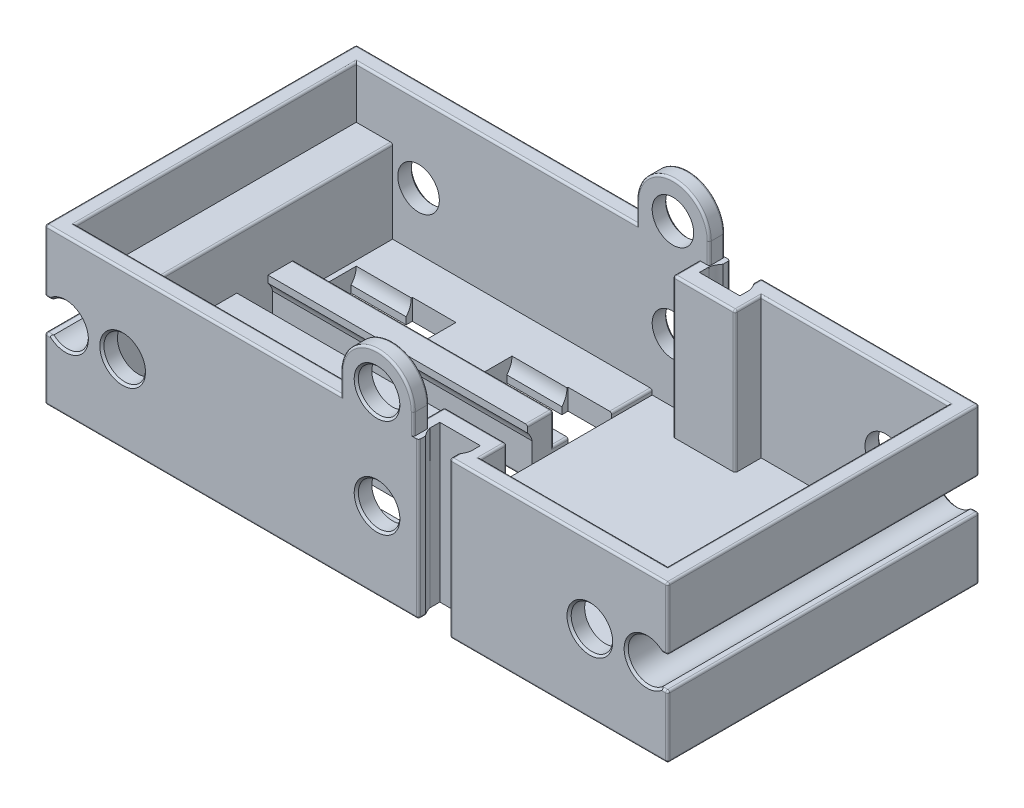
SolidWorks part; units mm, degrees
ref_plane "前视基准面" through (0, 0, 0) normal (0, 0, 1) x (1, 0, 0)
ref_plane "上视基准面" through (0, 0, 0) normal (0, 1, 0) x (1, 0, 0)
ref_plane "右视基准面" through (0, 0, 0) normal (1, 0, 0) x (0, 0, -1)
sketch "草图1" plane through (0, 0, 0) normal (0, 1, 0) x (1, 0, 0)
  line L0 (30, 15) -> (30, -15)
  line L1 (30, 15) -> (-30, 15)
  line L2 (30, -15) -> (-30, -15)
  line L3 (-30, 15) -> (-30, -15)
  line L4 (30, 15) -> (-30, -15) construction
  line L5 (30, -15) -> (-30, 15) construction
  point P1 (0, 0)
  dimension "D1" = 60
  dimension "D2" = 30
extrude "凸台-拉伸1" add sketch "草图1" along normal blind 15
sketch "草图2" plane through (0, 15, 0) normal (0, 1, 0) x (1, 0, 0)
  line L0 (28.5, 13.5) -> (28.5, -13.5)
  line L1 (28.5, 13.5) -> (10.5, 13.5)
  line L2 (28.5, -13.5) -> (10.5, -13.5)
  line L3 (-28.5, 13.5) -> (-28.5, -13.5)
  line L4 (28.5, 13.5) -> (-28.5, -13.5) construction
  line L5 (28.5, -13.5) -> (-28.5, 13.5) construction
  line L6 (28.5, 0) -> (10.5, 0) construction
  line L7 (10.5, 0) -> (4.5, 0) construction
  line L8 (4.5, 13.5) -> (4.5, 11)
  line L9 (10.5, 13.5) -> (10.5, 11)
  line L10 (10.5, 11) -> (4.5, 11)
  line L11 (10.5, -11) -> (4.5, -11)
  line L12 (4.5, 13.5) -> (-28.5, 13.5)
  line L13 (4.5, -13.5) -> (-28.5, -13.5)
  line L15 (4.5, -11) -> (4.5, -13.5)
  line L16 (10.5, -11) -> (10.5, -13.5)
  point P1 (0, 0)
  dimension "D1" = 27
  dimension "D2" = 57
  dimension "D3" = 18
  dimension "D4" = 6
  dimension "D5" = 11
  dimension "D6" = 11
extrude "切除-拉伸1" cut sketch "草图2" against normal blind 5
sketch "草图3" plane through (0, 10, 0) normal (0, 1, 0) x (1, 0, 0)
  line L0 (-30, 0) -> (-25, 0) construction
  line L1 (-30, 15) -> (-30, -15) construction
  line L2 (30, 0) -> (25, 0) construction
  line L3 (30, -15) -> (30, 15) construction
  line L4 (-25, 13.5) -> (-25, -13.5)
  line L5 (25, 13.5) -> (25, -13.5)
  line L12 (4.5, 13.5) -> (-28.5, 13.5)
  line L13 (-28.5, 13.5) -> (-28.5, -13.5)
  line L14 (-28.5, -13.5) -> (4.5, -13.5)
  line L15 (4.5, -13.5) -> (4.5, -11)
  line L16 (4.5, -11) -> (10.5, -11)
  line L17 (10.5, -11) -> (10.5, -13.5)
  line L18 (10.5, -13.5) -> (28.5, -13.5)
  line L19 (28.5, -13.5) -> (28.5, 13.5)
  line L20 (28.5, 13.5) -> (10.5, 13.5)
  line L21 (10.5, 13.5) -> (10.5, 11)
  line L22 (10.5, 11) -> (4.5, 11)
  line L23 (4.5, 11) -> (4.5, 13.5)
  line L24 (4.5, 13.5) -> (-25, 13.5)
  line L26 (-25, -13.5) -> (4.5, -13.5)
  line L27 (4.5, -13.5) -> (4.5, -11)
  line L28 (4.5, -11) -> (10.5, -11)
  line L29 (10.5, -11) -> (10.5, -13.5)
  line L30 (10.5, -13.5) -> (25, -13.5)
  line L32 (25, 13.5) -> (10.5, 13.5)
  line L33 (10.5, 13.5) -> (10.5, 11)
  line L34 (10.5, 11) -> (4.5, 11)
  line L35 (4.5, 11) -> (4.5, 13.5)
  dimension "D2" = 5
  dimension "D3" = 5
  dimension "D1" = 0
extrude "切除-拉伸2" cut sketch "草图3" against normal blind 8.5
sketch "草图4" plane through (0, 15, 0) normal (0, 1, 0) x (1, 0, 0)
  line L0 (7.5, -15) -> (7.5, -13) construction
  line L1 (-30, -15) -> (30, -15) construction
  line L2 (7.5, -13) -> (7.5, -12.5) construction
  line L3 (9, -15) -> (6, -15)
  line L4 (6, -15) -> (6, -14.3229)
  line L5 (9.45, -12.5) -> (5.55, -12.5)
  line L6 (5.55, -12.5) -> (5.55, -13.4444)
  line L7 (9, -15) -> (9, -14.3229)
  line L8 (9.45, -12.5) -> (9.45, -13.4444)
  arc A0 (5.55, -13.4444) -> (6, -14.3229) centre (7.5, -13) ccw
  arc A1 (9.45, -13.4444) -> (9, -14.3229) centre (7.5, -13) cw
  dimension "D6" = 2
  dimension "D1" = 2
  dimension "D2" = 0.5
  dimension "D3" = 3
  dimension "D4" = 1.95
  dimension "D5" = 1.5
extrude "切除-拉伸3" cut sketch "草图4" against normal up to next
mirror "镜向1" about plane through (0, 0, 0) normal (0, 0, 1) of "切除-拉伸3"
sketch "草图5" plane through (0, 0, 15) normal (0, 0, 1) x (1, 0, 0)
  line L0 (-30, 7.5) -> (-28, 7.5) construction
  line L1 (-30, 15) -> (-30, 0) construction
  line L2 (-28, 7.5) -> (-22.5, 7.5) construction
  line L3 (-30, 6) -> (-30, 9)
  line L4 (-30, 9) -> (-29.3229, 9)
  line L5 (-30, 6) -> (-29.3229, 6)
  arc A0 (-29.3229, 6) -> (-29.3229, 9) centre (-28, 7.5) ccw
  circle A1 centre (-22.5, 7.5) radius 2
  dimension "D3" = 4
  dimension "D5" = 2
  dimension "D1" = 2
  dimension "D2" = 5.5
  dimension "D4" = 1.5
extrude "切除-拉伸4" cut sketch "草图5" against normal through all
mirror "镜向2" about plane through (0, 0, 0) normal (1, 0, 0) of "切除-拉伸4"
sketch "草图6" plane through (0, 0, 0) normal (0, -1, 0) x (1, 0, 0)
  line L0 (-30, -15) -> (-30, 15) construction
  line L1 (-28.5, 13.5) -> (-26.5, 13.5)
  line L2 (-28.5, 13.5) -> (-28.5, -13.5)
  line L3 (-28.5, -13.5) -> (-26.5, -13.5)
  line L4 (-26.5, 13.5) -> (-26.5, -13.5)
  line L5 (-30, 15) -> (6, 15) construction
  line L6 (6, -15) -> (-30, -15) construction
  dimension "D1" = 1.5
  dimension "D2" = 1.5
  dimension "D3" = 1.5
  dimension "D4" = 2
extrude "切除-拉伸5" cut sketch "草图6" against normal blind 5
sketch "草图7" plane through (0, 5, 0) normal (0, -1, 0) x (1, 0, 0)
  line L0 (-26.5, 0) -> (-28.5, 0) construction
  line L1 (-26.5, -13.5) -> (-26.5, 13.5) construction
  line L2 (-28.5, 13.5) -> (-28.5, -13.5) construction
  line L3 (-26.5, 2) -> (-28.5, 2)
  line L4 (-26.5, -2) -> (-28.5, -2)
  line L5 (-26.5, 3.5) -> (-28.5, 3.5)
  line L6 (-26.5, -3.5) -> (-28.5, -3.5)
  line L7 (-28.5, 3.5) -> (-28.5, 2)
  line L8 (-28.5, -2) -> (-28.5, -3.5)
  line L9 (-26.5, -2) -> (-26.5, -3.5)
  line L10 (-26.5, 3.5) -> (-26.5, 2)
  dimension "D1" = 2
  dimension "D2" = 2
  dimension "D3" = 3.5
  dimension "D4" = 3.5
extrude "凸台-拉伸2" add sketch "草图7" along normal blind 2.5
mirror "镜向3" about plane through (0, 0, 0) normal (1, 0, 0) of "凸台-拉伸2", "切除-拉伸5"
sketch "草图8" plane through (0, 1.5, 0) normal (0, 1, 0) x (1, 0, 0)
  line L0 (-25, -13.5) -> (4.5, -13.5) construction
  line L1 (-25, 13.5) -> (0, 13.5)
  line L2 (-25, 13.5) -> (-25, -13.5)
  line L3 (-25, -13.5) -> (0, -13.5)
  line L4 (0, 13.5) -> (0, -13.5)
  dimension "D1" = 25
extrude "凸台-拉伸3" add sketch "草图8" along normal blind 0.5
sketch "草图9" plane through (0, 2, 0) normal (0, 1, 0) x (1, 0, 0)
  line L1 (-4.2, 5.4) -> (0, 5.4)
  line L2 (-4.2, 5.4) -> (-4.2, 9.6)
  line L3 (0, 5.4) -> (0, 9.6)
  line L4 (-4.2, 9.6) -> (0, 9.6)
  line L5 (-4.2, 5.4) -> (0, 9.6) construction
  line L6 (0, 5.4) -> (-4.2, 9.6) construction
  line L7 (6, 15) -> (-30, 15) construction
  line L10 (0, -13.5) -> (0, 13.5) construction
  point P1 (-2.1, 7.5)
  dimension "D1" = 4.2
  dimension "D2" = 4.2
  dimension "D3" = 7.5
  dimension "D4" = 2.1
extrude "切除-拉伸6" cut sketch "草图9" against normal up to next
sketch "草图10" plane through (-4.2, 0, 0) normal (1, 0, 0) x (0, 0, -1)
  line L0 (15, 0) -> (7.5, 0) construction
  line L1 (-15, 0) -> (15, 0) construction
  line L2 (7.5, 0) -> (7.5, 2) construction
  line L3 (9, 0) -> (6, 0)
  line L4 (6, 0) -> (6, 0.6771)
  line L5 (9, 0) -> (9, 0.6771)
  arc A0 (9, 0.6771) -> (6, 0.6771) centre (7.5, 2) ccw
  dimension "D1" = 7.5
  dimension "D2" = 2
  dimension "D3" = 1.5
extrude "切除-拉伸7" cut sketch "草图10" against normal blind 5.3
pattern_linear "阵列(线性)1" count 2 spacing 15 along (-1, 0, 0) count 2 spacing 15 along (0, 0, 1) of "切除-拉伸6", "切除-拉伸7"
sketch "草图13" plane through (-25, 0, 0) normal (1, 0, 0) x (0, 0, -1)
  line L0 (4, 5) -> (4, 0)
  line L1 (4, 5) -> (-4, 5)
  line L2 (4, 0) -> (-4, 0)
  line L3 (-4, 5) -> (-4, 0)
  line L4 (4, 5) -> (-4, 0) construction
  line L5 (4, 0) -> (-4, 5) construction
  point P1 (0, 2.5)
  dimension "D1" = 2.5
  dimension "D2" = 0
  dimension "D3" = 8
  dimension "D4" = 5
extrude "凸台-拉伸4" add sketch "草图13" along normal blind 25
sketch "草图14" plane through (0, 0, 0) normal (1, 0, 0) x (0, 0, -1)
  line L0 (0, 15) -> (0, 5) construction
  line L1 (-15, 15) -> (15, 15) construction
  line L2 (0, 5) -> (0, 3) construction
  line L3 (0, 3) -> (0, 2.2) construction
  line L4 (1.5, 5) -> (-1.5, 5)
  line L5 (-1.5, 5) -> (-1.5, 4.3229)
  line L6 (0, 2.2) -> (-1.95, 2.2) construction
  line L7 (-1.95, 0) -> (-1.95, 3.4444)
  line L8 (-15, 0) -> (15, 0) construction
  line L9 (1.95, 0) -> (-1.95, 0)
  line L10 (1.95, 0) -> (1.95, 3.4444)
  line L11 (1.5, 5) -> (1.5, 4.3229)
  arc A0 (1.5, 4.3229) -> (1.95, 3.4444) centre (0, 3) cw
  arc A1 (-1.5, 4.3229) -> (-1.95, 3.4444) centre (0, 3) ccw
  point P16 (0, 0)
  dimension "D6" = 2
  dimension "D1" = 10
  dimension "D2" = 2
  dimension "D3" = 0.8
  dimension "D4" = 1.5
  dimension "D5" = 1.95
extrude "切除-拉伸8" cut sketch "草图14" against normal blind 25
sketch "草图15" plane through (0, 0, -15) normal (0, 0, -1) x (-1, 0, 0)
  line L0 (0, 0) -> (-2, 0) construction
  line L1 (-6, 0) -> (30, 0) construction
  line L2 (-2, 0) -> (-2, 17) construction
  line L3 (-5.5, 17) -> (-5.5, 15)
  line L4 (1.5, 17) -> (1.5, 15)
  line L5 (-2, 17) -> (-2, 15) construction
  line L6 (1.5, 15) -> (-5.5, 15)
  line L7 (-6, 15) -> (30, 15) construction
  arc A0 (1.5, 17) -> (-5.5, 17) centre (-2, 17) ccw
  dimension "D3" = 7
  dimension "D1" = 2
  dimension "D2" = 17
  dimension "D4" = 2
extrude "凸台-拉伸5" add sketch "草图15" against normal blind 1.5
sketch "草图16" plane through (0, 0, -15) normal (0, 0, -1) x (-1, 0, 0)
  line L0 (-6, 0) -> (30, 0) construction
  circle A0 centre (-2, 17) radius 2
  circle A1 centre (-2, 7.5) radius 2
  dimension "D1" = 4
  dimension "D3" = 4
  dimension "D2" = 7.5
  dimension "D4" = 2
extrude "切除-拉伸9" cut sketch "草图16" against normal up to next
mirror "镜向4" about plane through (0, 0, 0) normal (0, 0, 1) of "切除-拉伸9", "凸台-拉伸5"
fillet "圆角1" radius 0.2 44 edges at (-1.5, 16, -15) (5.5, 16, -15) (-1.5, 16, -13.5) (5.5, 16, -13.5) (-1.5, 16, 13.5) (5.5, 16, 13.5) (-1.5, 16, 15) (5.5, 16, 15) (-30, 0, 0) (-12, 0, 15) (-12, 0, -15) (19.5, 0, -15) (19.5, 0, 15) (30, 0, 0) (30, 3, -15) (30, 12, -15) (30, 3, 15) (30, 12, 15) (-30, 3, -15) (-30, 12, -15) (-30, 3, 15) (-30, 12, 15) (2, 20.5, -15) (2, 20.5, -13.5) (2, 20.5, 13.5) (2, 20.5, 15) (4.5, 15, 12.25) (7.5, 15, 11) (10.5, 15, 12.25) (19.5, 15, 13.5) (19.5, 15, 15) (28.5, 15, 0) (30, 15, 0) (19.5, 15, -15) (19.5, 15, -13.5) (10.5, 15, -12.25) (7.5, 15, -11) (4.5, 15, -12.25) (-15, 15, 13.5) (-15.75, 15, 15) (-28.5, 15, 0) (-15, 15, -13.5) (-15.75, 15, -15) (-30, 15, 0)
fillet "圆角2" radius 0.2 22 edges at (10.4414, 14.9414, 11.0586) (4.5586, 14.9414, 11.0586) (10.4414, 14.9414, -11.0586) (4.5586, 14.9414, -11.0586) (0, 0, 0) (-12.5, 0, -1.95) (-25, 0, 0) (-12.5, 0, 1.95) (-27.5, 0, -13.5) (-28.5, 0, 0) (-27.5, 0, 13.5) (-26.5, 0, 0) (27.5, 0, -13.5) (26.5, 0, 0) (27.5, 0, 13.5) (28.5, 0, 0) (10.5, 8.15, 11) (4.5, 8.15, 11) (10.5, 8.15, -11) (4.5, 8.15, -11)
fillet "圆角3" radius 0.2 10 edges at (-12.5, 5, 4) (-12.5, 5, -4) (0, 2, 11.55) (0, 2, 4.7) (0, 2, -4.7) (0, 2, -11.55) (0, 3.5, 4) (0, 3.5, -4) (0, 5, 2.75) (0, 5, -2.75)
chamfer "倒角1" distance 0.2 angle 45 12 edges at (-26, 7.5, -15) (-20.5, 7.5, -15) (0, 7.5, -15) (0, 17, -15) (26, 7.5, -15) (20.5, 7.5, -15) (26, 7.5, 15) (20.5, 7.5, 15) (0, 17, 15) (0, 7.5, 15) (-20.5, 7.5, 15) (-26, 7.5, 15)
fillet "圆角4" radius 0.2 36 edges at (9, 0, -14.5614) (9, 0.0586, -14.9414) (9, 15, -14.5614) (9, 14.9414, -14.9414) (6, 0, -14.5614) (6, 0.0586, -14.9414) (6, 0, 14.5614) (6, 0.0586, 14.9414) (9, 0, 14.5614) (9, 0.0586, 14.9414) (9, 15, 14.5614) (9, 14.9414, 14.9414) (29.7047, 9, -15) (29.9414, 9, -14.9414) (29.7047, 9, 15) (29.9414, 9, 14.9414) (29.7047, 6, -15) (29.9414, 6, -14.9414) (29.7047, 6, 15) (29.9414, 6, 14.9414) (-29.7047, 9, -15) (-29.9414, 9, -14.9414) (-29.7047, 9, 15) (-29.9414, 9, 14.9414) (-29.7047, 6, -15) (-29.9414, 6, -14.9414) (-29.7047, 6, 15) (-29.9414, 6, 14.9414) (9, 7.5, -15) (6, 7.6, -15) (6, 7.6, 15) (9, 7.5, 15) (30, 9, 0) (30, 6, 0) (-30, 9, 0) (-30, 6, 0)
